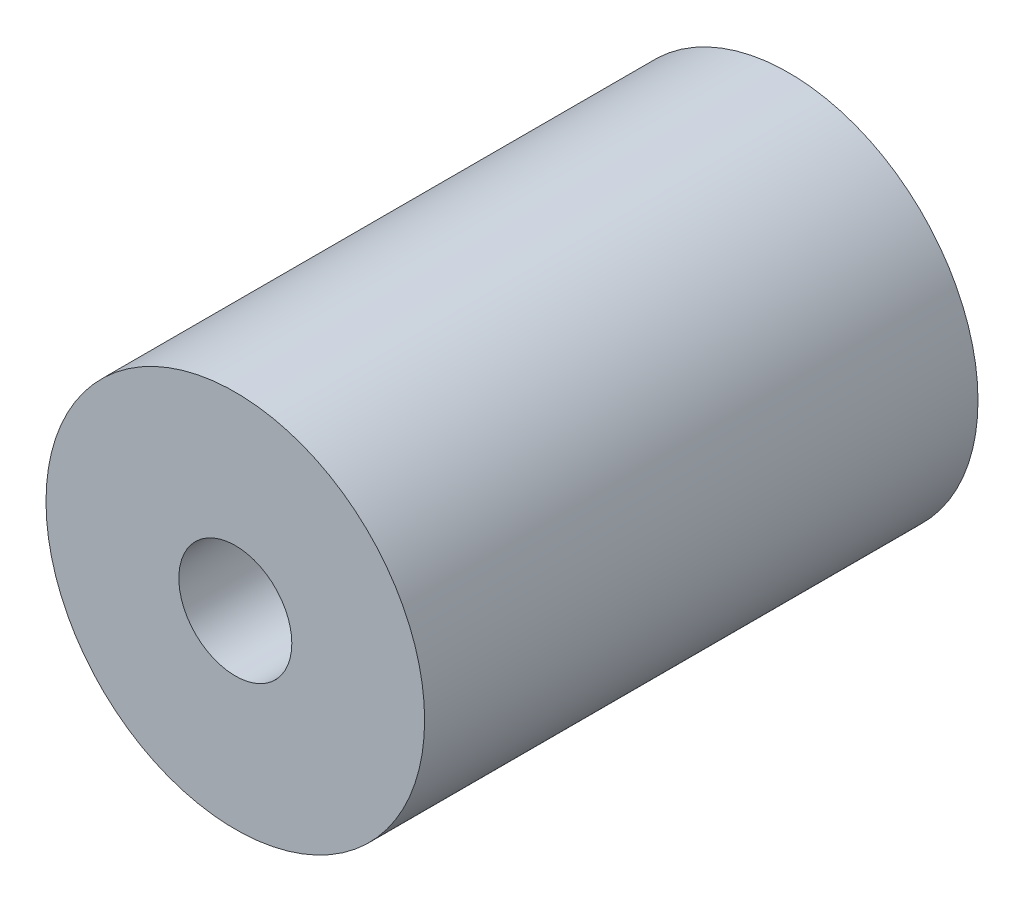
SolidWorks part; units mm, degrees
ref_plane "Front Plane" through (0, 0, 0) normal (0, 0, 1) x (1, 0, 0)
ref_plane "Top Plane" through (0, 0, 0) normal (0, 1, 0) x (1, 0, 0)
ref_plane "Right Plane" through (0, 0, 0) normal (1, 0, 0) x (0, 0, -1)
sketch "Sketch1" plane through (0, 0, 0) normal (0, 0, 1) x (1, 0, 0)
  circle A0 centre (0, 0) radius 2.5527
  circle A1 centre (0, 0) radius 8.5527
  dimension "D1" = 5.1054
  dimension "D2" = 6
extrude "Boss-Extrude1" add sketch "Sketch1" along normal mid plane 25
